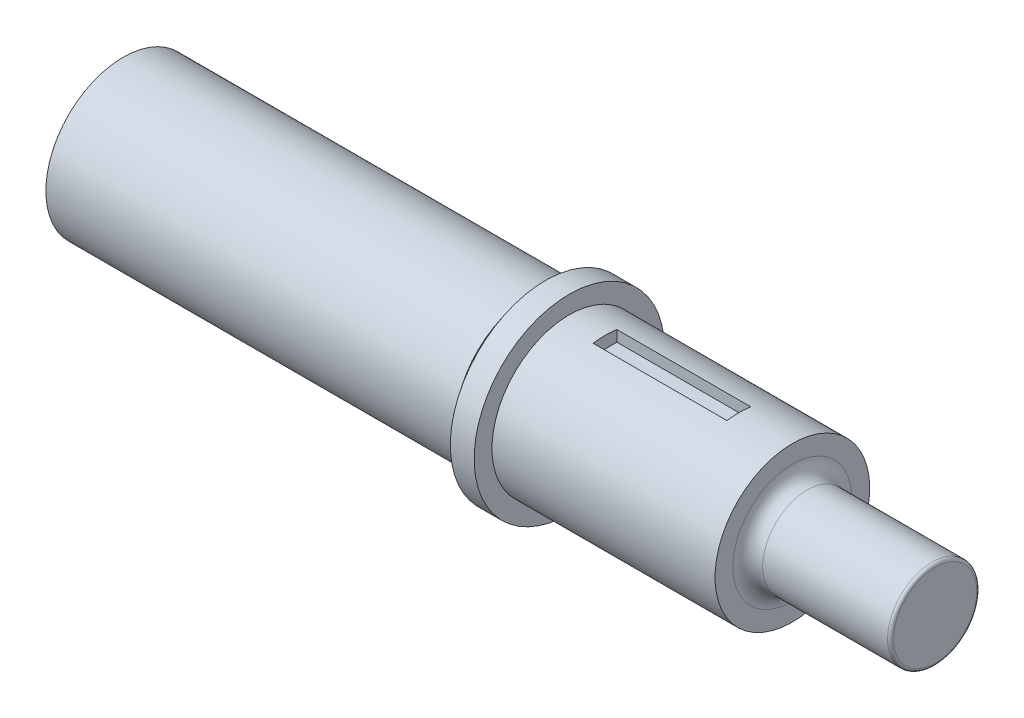
SolidWorks part; units mm, degrees
ref_plane "Front Plane" through (0, 0, 0) normal (0, 0, 1) x (1, 0, 0)
ref_plane "Top Plane" through (0, 0, 0) normal (0, 1, 0) x (1, 0, 0)
ref_plane "Right Plane" through (0, 0, 0) normal (1, 0, 0) x (0, 0, -1)
sketch "Sketch1" plane through (0, 0, 0) normal (1, 0, 0) x (0, 0, -1)
  circle A0 centre (0, 0) radius 26
extrude "Boss-Extrude1" add sketch "Sketch1" along normal blind 137.5
sketch "Sketch2" plane through (137.5, 0, 0) normal (1, 0, 0) x (0, 0, -1)
  circle A0 centre (0, 0) radius 22
extrude "Boss-Extrude2" add sketch "Sketch2" along normal blind 4.5
sketch "Sketch3" plane through (142, 0, 0) normal (1, 0, 0) x (0, 0, -1)
  circle A0 centre (0, 0) radius 32
extrude "Boss-Extrude3" add sketch "Sketch3" along normal blind 8
sketch "Sketch4" plane through (150, 0, 0) normal (1, 0, 0) x (0, 0, -1)
  circle A0 centre (0, 0) radius 26
extrude "Boss-Extrude4" add sketch "Sketch4" along normal blind 75
hole_wizard "Ø12.0 (12) Diameter Hole1" positions "3DSketch1" profile "Sketch5" hole size "Ø12.0" standard "ISO"
sketch3d "3DSketch1"
  line L0 (137.5, 0, 0) -> (0, 0, 0) construction
  point P0 (0, 0, 0)
  point P3 (0, 0, 0)
  point P6 (0, 0, 0)
  point P8 (0, 0, 0)
  point P12 (-153.5637, 12.3509, 0)
  point P14 (0, 0, 0)
  point P16 (0, 0, 0)
  point P18 (0, 0, 0)
  dimension "D1" = 0
sketch "Sketch5" plane through (0, 0, 0) normal (0, 1, 0) x (0, 0, 1)
  line L0 (0, 0) -> (0, 23.6052)
  line L1 (0, 23.6052) -> (6, 20)
  line L2 (6, 20) -> (6, 0)
  line L5 (6, 0) -> (0, 0)
  line L10 (0, 23.6052) -> (-6, 20) construction
  line L11 (0, -6.35) -> (0, 107.95) construction
  dimension "Hole Dia." = 12
  dimension "Hole Depth" = 20
  dimension "Drill Angle" = 118
cosmetic thread "Représentation de filetage1" parameters "D2"=13
cosmetic thread "Représentation de filetage2" parameters "D2"=13
sketch "Sketch6" plane through (225, 0, 0) normal (1, 0, 0) x (0, 0, -1)
  circle A0 centre (0, 0) radius 15
extrude "Boss-Extrude5" add sketch "Sketch6" along normal blind 48
cosmetic thread "Cosmetic Thread1" parameters "D1"=29, "D2"=27.797
fillet "Fillet2" radius 5 1 edges at (225, 0, -15)
sketch "Sketch7" plane through (0, 0, 0) normal (0, 1, 0) x (1, 0, 0)
  line L0 (225, 26) -> (150, 26) construction
  line L1 (162, -4) -> (207, -4)
  line L2 (162, -4) -> (162, 4)
  line L3 (162, 4) -> (207, 4)
  line L4 (207, -4) -> (207, 4)
  line L5 (150, -26) -> (225, -26) construction
  line L7 (150, -32) -> (150, 32) construction
  dimension "D1" = 30
  dimension "D2" = 30
  dimension "D4" = 12
  dimension "D3" = 45
extrude "Cut-Extrude1" cut sketch "Sketch7" against normal blind 4 from offset 26
sketch "Esquisse1" plane through (0, 0, 0) normal (-1, 0, 0) x (0, 0, 1)
  line L0 (0, -6) -> (0, -26) construction
  circle A0 centre (0, 0) radius 26 construction
  circle A4 centre (0, 0) radius 6 construction
  circle A5 centre (0, 0) radius 6 construction
  point P14 (0, -16)
  dimension "D1" = 20
  dimension "D2" = 0
hole_wizard "M8 Clearance Hole1" positions "Esquisse1" profile "Esquisse3" hole size "M8" standard "ANSI Metric"
sketch "Esquisse3" plane through (0, -16, 0) normal (0, 1, 0) x (0, 0, 1)
  line L0 (0, 0) -> (0, 15.5236)
  line L1 (0, 15.5236) -> (4.2, 13)
  line L2 (4.2, 13) -> (4.2, 0)
  line L5 (4.2, 0) -> (0, 0)
  line L10 (0, 15.5236) -> (-4.2, 13) construction
  line L11 (0, -6.35) -> (0, 107.95) construction
  dimension "Diamètre du perçage" = 8.4
  dimension "Profondeur du perçage" = 13
  dimension "Angle de pointe" = 118
cosmetic thread "Représentation de filetage3" parameters "D2"=10
cosmetic thread "Représentation de filetage4" parameters "D2"=10
sketch "Sketch8" plane through (0, 0, 0) normal (0, 0, 1) x (1, 0, 0)
  line L0 (150, 0) -> (244, 0) construction
  line L1 (150, -32) -> (150, 32) construction
  line L2 (244, 0) -> (273, 0) construction
  line L3 (273, -15) -> (273, 15) construction
  dimension "D1" = 94
  dimension "D2" = 123
sketch "Sketch9" plane through (0, 0, 0) normal (0, 0, 1) x (1, 0, 0)
  line L0 (0, 0) -> (150, 0) construction
  line L1 (0, 26) -> (0, -26) construction
  line L2 (142, 32) -> (142, -32) construction
  point P5 (142, 0)
fillet "Fillet3" radius 1 1 edges at (273, 0, -15)
equation "\"D2@Sketch7\"=\"D1@Sketch7\""
